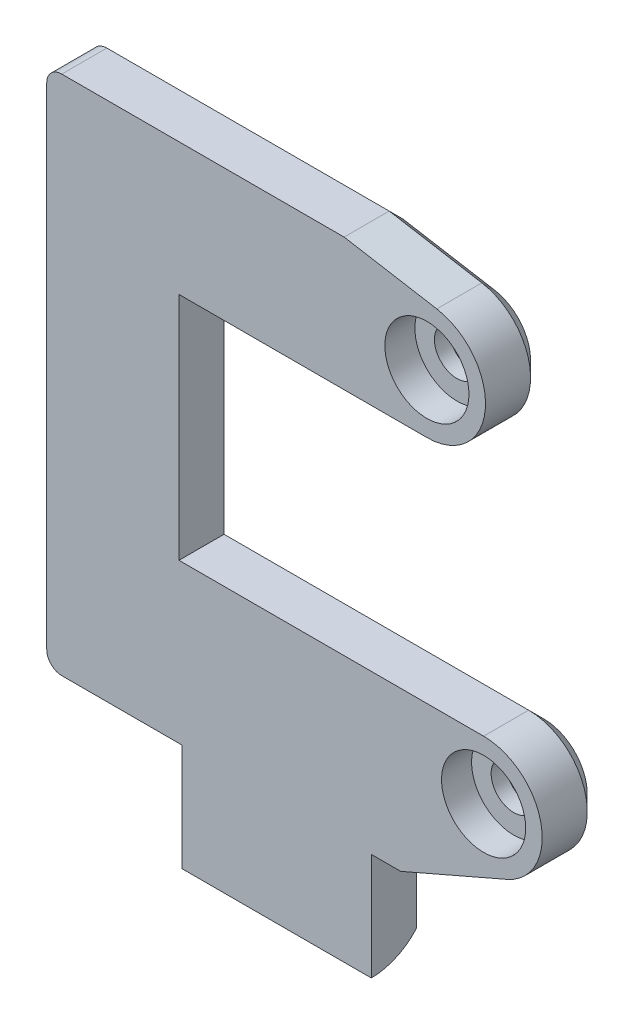
SolidWorks part; units mm, degrees
ref_plane "Front" through (0, 0, 0) normal (0, 0, 1) x (1, 0, 0)
ref_plane "Top" through (0, 0, 0) normal (0, 1, 0) x (1, 0, 0)
ref_plane "Right" through (0, 0, 0) normal (1, 0, 0) x (0, 0, -1)
sketch "Sketch1" plane through (0, 0, 0) normal (0, 0, 1) x (1, 0, 0)
  line L36 (-6.3, -24.9) -> (6.3, -24.9)
  line L37 (6.3, -24.9) -> (6.3, -17.775)
  line L38 (6.3, -17.775) -> (8.2542, -17.775)
  line L52 (8.2542, -17.775) -> (15.3288, -14.7021)
  line L53 (13.775, -7.225) -> (-6.5, -7.225)
  line L54 (-6.5, -7.225) -> (-6.5, 8.1)
  line L55 (-6.5, 8.1) -> (10, 8.1)
  line L56 (10.6582, 15.8441) -> (4.4915, 16.9)
  line L57 (4.4915, 16.9) -> (-15.3, 16.9)
  line L58 (-15.3, 16.9) -> (-15.3, -17.775)
  line L59 (-15.3, -17.775) -> (-6.3, -17.775)
  line L60 (-6.3, -17.775) -> (-6.3, -24.9)
  line L61 (-6.3, -24.9) -> (6.3, -24.9)
  line L62 (6.3, -24.9) -> (6.3, -17.775)
  line L63 (6.3, -17.775) -> (8.2542, -17.775)
  line L64 (8.2542, -17.775) -> (15.3288, -14.7021)
  line L65 (13.775, -7.225) -> (-6.5, -7.225)
  line L66 (-6.5, -7.225) -> (-6.5, 8.1)
  line L67 (-6.5, 8.1) -> (10, 8.1)
  line L68 (10.6582, 15.8441) -> (4.4915, 16.9)
  line L69 (4.4915, 16.9) -> (-15.3, 16.9)
  line L70 (-15.3, 16.9) -> (-15.3, -17.775)
  line L71 (-15.3, -17.775) -> (-6.3, -17.775)
  line L72 (-6.3, -17.775) -> (-6.3, -24.9)
  arc A8 (15.3288, -14.7021) -> (13.775, -7.225) centre (13.775, -11.125) ccw
  arc A9 (10, 8.1) -> (10.6582, 15.8441) centre (10, 12) ccw
  arc A10 (15.3288, -14.7021) -> (13.775, -7.225) centre (13.775, -11.125) ccw
  arc A11 (10, 8.1) -> (10.6582, 15.8441) centre (10, 12) ccw
  dimension "D1" = 0.1
extrude "Boss-Extrude1" add sketch "Sketch1" along normal up to surface (4 mm away)
sketch "Sketch2" plane through (-15.3, 0, 0) normal (-1, 0, 0) x (0, 0, 1)
  line L1 (1, -14) -> (3, -14)
  line L2 (1, -14) -> (1, -5)
  line L3 (1, -5) -> (3, -5)
  line L4 (3, -14) -> (3, -5)
  line L5 (1, 5) -> (3, 5)
  line L6 (1, 5) -> (1, 14)
  line L7 (1, 14) -> (3, 14)
  line L8 (3, 5) -> (3, 14)
extrude "Boss-Extrude2" add sketch "Sketch2" along normal blind 1 draft 45
sketch "Sketch3" plane through (0, 0, 0) normal (0, 0, -1) x (-1, 0, 0)
  circle A2 centre (-10, 12) radius 1.5
  circle A3 centre (-10, 12) radius 1.5
  dimension "D1" = 0
extrude "Cut-Extrude1" cut sketch "Sketch3" against normal through all
sketch "Sketch4" plane through (0, 0, 0) normal (0, 0, -1) x (-1, 0, 0)
  circle A2 centre (-13.775, -11.125) radius 1.5
  circle A3 centre (-13.775, -11.125) radius 1.5
  dimension "D1" = 0
extrude "Cut-Extrude2" cut sketch "Sketch4" against normal through all
fillet "Fillet2" radius 1 2 edges at (-15.3, 16.9, 2) (-15.3, -17.775, 2)
fillet "Fillet3" radius 1 17 edges at (8.5, 12, 0) (12.275, -11.125, 0) (-15.0071, -17.4821, 0) (-10.3, -17.775, 0) (-6.3, -21.3375, 0) (6.3, -21.3375, 0) (7.2771, -17.775, 0) (11.7915, -16.2386, 0) (17.5934, -10.3315, 0) (3.6375, -7.225, 0) (-6.5, 0.4375, 0) (1.75, 8.1, 0) (13.886, 11.6697, 0) (7.5749, 16.372, 0) (-4.9042, 16.9, 0) (-15.0071, 16.6071, 0) (-15.3, -0.4375, 0) profile chamfer
sketch "Sketch5" plane through (0, 0, 4) normal (0, 0, 1) x (1, 0, 0)
  circle A0 centre (13.775, -11.125) radius 2.8
  circle A1 centre (10, 12) radius 2.8
  dimension "D1" = 5.6
extrude "Cut-Extrude3" cut sketch "Sketch5" against normal blind 2
fillet "Fillet4" radius 4 1 edges at (0, -24.9, 0)
